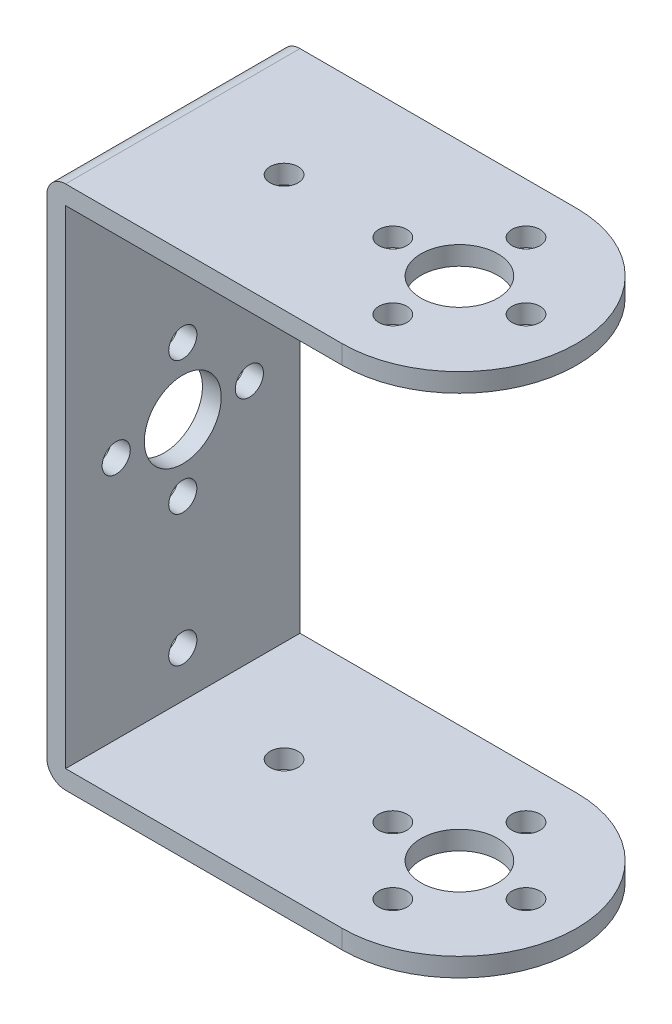
SolidWorks part; units mm, degrees
ref_plane "前视基准面" through (0, 0, 0) normal (0, 0, 1) x (1, 0, 0)
ref_plane "上视基准面" through (0, 0, 0) normal (0, 1, 0) x (1, 0, 0)
ref_plane "右视基准面" through (0, 0, 0) normal (1, 0, 0) x (0, 0, -1)
sketch "草图1" plane through (0, 0, 0) normal (0, 1, 0) x (1, 0, 0)
  line L1 (22, -12.5) -> (-22, -12.5)
  line L2 (22, -12.5) -> (22, 12.5)
  line L3 (22, 12.5) -> (-22, 12.5)
  line L4 (-22, -12.5) -> (-22, 12.5)
  line L5 (22, -12.5) -> (-22, 12.5) construction
  line L6 (22, 12.5) -> (-22, -12.5) construction
  point P0 (0, 0)
  dimension "D1" = 44
  dimension "D2" = 25
extrude "凸台-拉伸1" add sketch "草图1" against normal blind 2
sketch "草图2" plane through (0, 0, 0) normal (0, 1, 0) x (1, 0, 0)
  line L0 (-22, -12.5) -> (22, -12.5) construction
  line L1 (-22, 12.5) -> (-20, 12.5)
  line L2 (-22, 12.5) -> (-22, -12.5)
  line L3 (-22, -12.5) -> (-20, -12.5)
  line L4 (-20, 12.5) -> (-20, -12.5)
  dimension "D1" = 2
extrude "凸台-拉伸2" add sketch "草图2" against normal blind 56
ref_plane "基准面1" through (0, -28, 0) normal (0, 1, 0) x (1, 0, 0)
fillet "圆角1" 2 edges at (22, -1, 12.5) (22, -1, -12.5) type full round first side face at (-6.6667, -19.3333, 12.5) second side face at (-6.6667, -19.3333, -12.5) middle face at (22, -1, 0)
sketch "草图3" plane through (0, 0, 0) normal (0, 1, 0) x (1, 0, 0)
  line L0 (-29.3505, 0) -> (38.6848, 0) construction
  line L1 (9.5, 7.9337) -> (9.5, -10.0875) construction
  circle A0 centre (9.5, 0) radius 4.1
  arc A1 (9.5, -12.5) -> (9.5, 12.5) centre (9.5, 0) ccw construction
  circle A2 centre (2.4, 0) radius 1.5
  circle A3 centre (9.5, 7.1) radius 1.5
  circle A4 centre (16.6, 0) radius 1.5
  circle A5 centre (9.5, -7.1) radius 1.5
  circle A6 centre (-9.2, 0) radius 1.5
  point P21 (9.5, 0)
  dimension "D1" = 8.2
  dimension "D2" = 8.4
  dimension "D3" = 3
  dimension "D4" = 1.5
  dimension "D6" = 3
  dimension "D7" = 8.6
  dimension "D5" = 4
extrude "切除-拉伸2" cut sketch "草图3" against normal up to next
mirror "镜向2" about plane through (0, -28, 0) normal (0, 1, 0) of bodies 110
sketch "草图4" plane through (-22, 0, 0) normal (-1, 0, 0) x (0, 0, 1)
  line L0 (-20.9506, -28) -> (27.7596, -28) construction
  line L1 (-12.5, -56) -> (-12.5, 0) construction
  line L2 (0, 1.1438) -> (0, -59.7626) construction
  circle A0 centre (0, -28) radius 4.1
  circle A1 centre (0, -20.9) radius 1.5
  circle A2 centre (7.1, -28) radius 1.5
  circle A3 centre (0, -35.1) radius 1.5
  circle A4 centre (-7.1, -28) radius 1.5
  circle A5 centre (0, -6.9) radius 1.5
  circle A6 centre (0, -49.1) radius 1.5
  point P4 (-12.5, -28)
  point P21 (0, -28)
  dimension "D1" = 8.2
  dimension "D2" = 3
  dimension "D3" = 1.5
  dimension "D5" = 3
  dimension "D6" = 11
  dimension "D4" = 4
extrude "切除-拉伸3" cut sketch "草图4" against normal up to next
fillet "圆角2" radius 2 2 edges at (-22, -56, 0) (-22, 0, 0)
